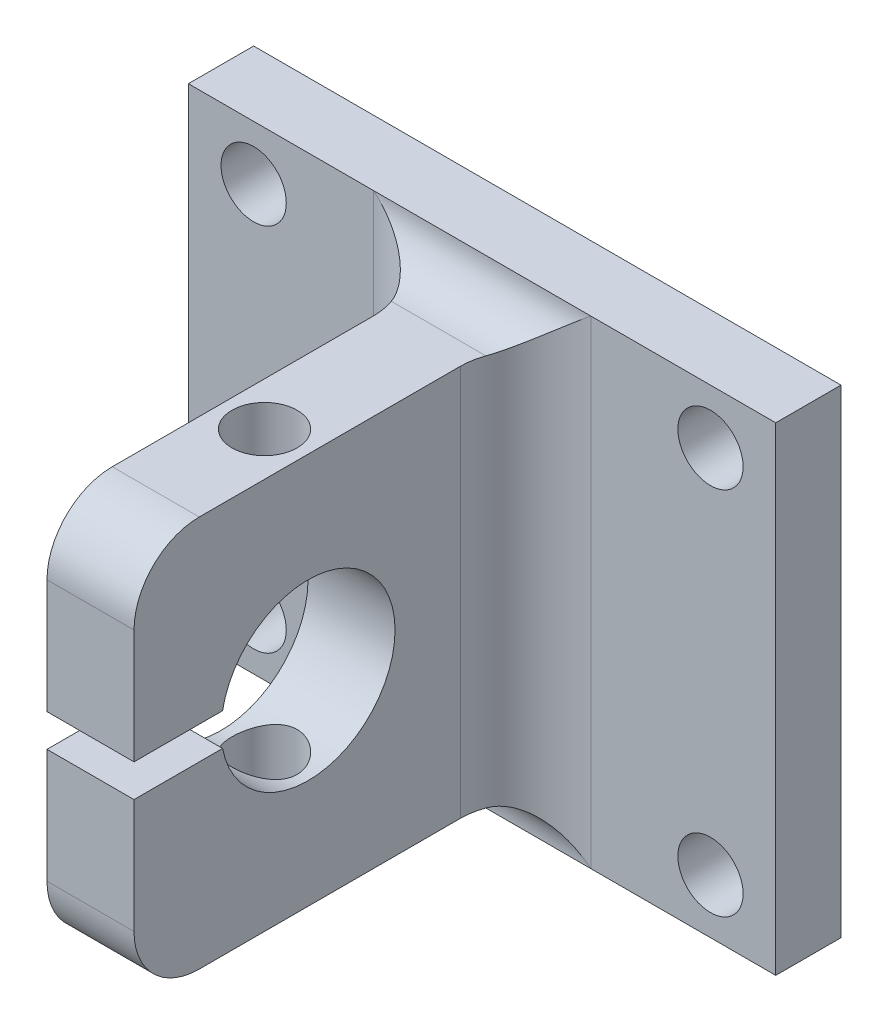
SolidWorks part; units mm, degrees
ref_plane "Front Plane" through (0, 0, 0) normal (0, 0, 1) x (1, 0, 0)
ref_plane "Top Plane" through (0, 0, 0) normal (0, 1, 0) x (1, 0, 0)
ref_plane "Right Plane" through (0, 0, 0) normal (1, 0, 0) x (0, 0, -1)
sketch "Sketch1" plane through (0, 0, 0) normal (0, 0, 1) x (1, 0, 0)
  line L1 (-13.5, -11) -> (13.5, -11)
  line L2 (-13.5, -11) -> (-13.5, 11)
  line L3 (-13.5, 11) -> (13.5, 11)
  line L4 (13.5, -11) -> (13.5, 11)
  line L5 (-13.5, -11) -> (13.5, 11) construction
  line L6 (-13.5, 11) -> (13.5, -11) construction
  line L7 (-10.5, -8.5) -> (-10.5, 8.5) construction
  line L8 (-10.5, 8.5) -> (10.5, 8.5) construction
  circle A5 centre (-10.5, -8.5) radius 1.5
  circle A6 centre (-10.5, 8.5) radius 1.5
  circle A7 centre (10.5, 8.5) radius 1.5
  circle A8 centre (10.5, -8.5) radius 1.5
  point P0 (0, 0)
  point P11 (-13.5, 0)
  point P12 (0, 11)
  point P13 (-10.5, 0)
  point P21 (0, 8.5)
  point P23 (0, 0)
  dimension "D5" = 3
  dimension "D1" = 27
  dimension "D2" = 22
  dimension "D6" = 17
  dimension "D7" = 21
extrude "Boss-Extrude1" add sketch "Sketch1" along normal blind 3
sketch "Sketch2" plane through (0, 0, 3) normal (0, 0, 1) x (1, 0, 0)
  line L1 (-2, 9) -> (2, 9)
  line L2 (-2, 9) -> (-2, -9)
  line L3 (-2, -9) -> (2, -9)
  line L4 (2, 9) -> (2, -9)
  line L5 (-13.5, -11) -> (13.5, -11) construction
  line L6 (2, 3.6093) -> (-2, 3.6093) construction
  line L7 (-13.5, 11) -> (-13.5, -11) construction
  point P4 (-13.5, 0)
  point P10 (0, -11)
  point P11 (0, 3.6093)
  point P12 (0, 0)
  point P13 (0, 0)
  point P14 (0, 0)
  point P16 (-2, 0)
  dimension "D1" = 4
  dimension "D2" = 18
extrude "Boss-Extrude2" add sketch "Sketch2" along normal blind 18
sketch "Sketch3" plane through (2, 0, 0) normal (1, 0, 0) x (0, 0, -1)
  line L0 (-21, -9) -> (-21, 9) construction
  line L1 (-3, -9) -> (-3, 9) construction
  circle A0 centre (-13, 0) radius 4
  point P5 (-21, 0)
  dimension "D1" = 8
  dimension "D2" = 10
extrude "Cut-Extrude1" cut sketch "Sketch3" against normal through all both and the other way through all
sketch "Sketch4" plane through (2, 0, 0) normal (1, 0, 0) x (0, 0, -1)
  line L1 (-22.3796, -0.75) -> (-14.282, -0.75)
  line L2 (-22.3796, -0.75) -> (-22.3796, 0.75)
  line L3 (-22.3796, 0.75) -> (-14.282, 0.75)
  line L4 (-14.282, -0.75) -> (-14.282, 0.75)
  line L5 (-21, -9) -> (-21, 9) construction
  point P6 (-21, 0)
  point P7 (-22.3796, 0)
  dimension "D1" = 1.5
extrude "Cut-Extrude2" cut sketch "Sketch4" against normal through all both and the other way through all
sketch "Sketch5" plane through (0, 11, 0) normal (0, 1, 0) x (1, 0, 0)
  line L0 (2, -21) -> (-2, -21) construction
  line L2 (2, -3) -> (-2, -3) construction
  circle A0 centre (0, -13) radius 1.5
  point P2 (0, 0)
  point P5 (0, -21)
  point P9 (0, 0)
  dimension "D1" = 3
  dimension "D2" = 10
fillet "Fillet1" radius 3 2 edges at (-2, 0, 3) (2, 0, 3)
extrude "Cut-Extrude3" cut sketch "Sketch5" against normal through all both and the other way through all
fillet "Fillet2" radius 2 2 edges at (0, 9, 3) (0, -9, 3)
fillet "Fillet3" radius 3 2 edges at (0, -9, 21) (0, 9, 21)
